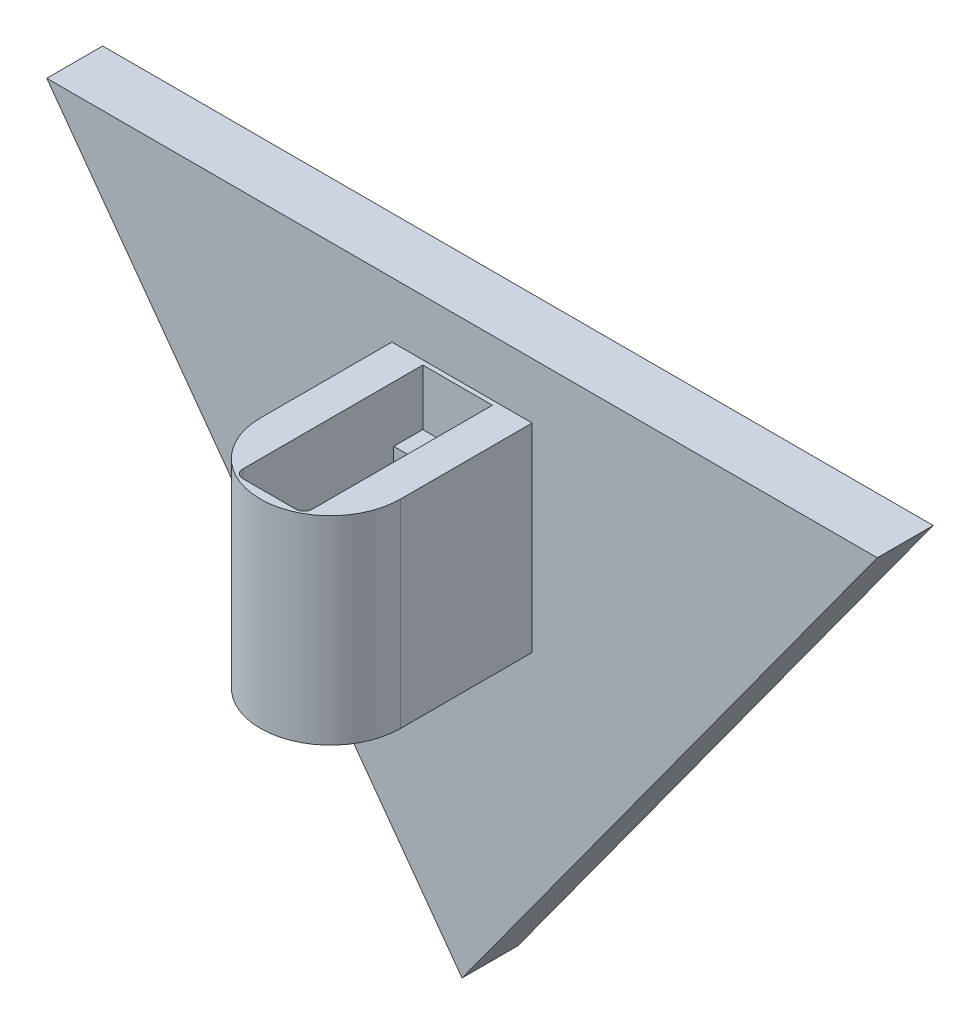
SolidWorks part; units mm, degrees
ref_plane "Front Plane" through (0, 0, 0) normal (0, 0, 1) x (1, 0, 0)
ref_plane "Top Plane" through (0, 0, 0) normal (0, 1, 0) x (1, 0, 0)
ref_plane "Right Plane" through (0, 0, 0) normal (1, 0, 0) x (0, 0, -1)
sketch "Sketch4" plane through (0, 0, 0) normal (0, 0, 1) x (1, 0, 0)
  line L0 (55, 0) -> (-55, 0) construction
  line L1 (-6.23, -9.975) -> (6.23, -9.975)
  line L2 (-6.23, -9.975) -> (-6.23, 7.275)
  line L3 (-6.23, 7.275) -> (6.23, 7.275)
  line L4 (6.23, -9.975) -> (6.23, 7.275)
  point P4 (0, 7.275)
  dimension "D1" = 12.46
  dimension "D2" = 17.25
  dimension "D3" = 9.975
extrude "Boss-Extrude3" add sketch "Sketch4" along normal blind 6
sketch "Sketch8" plane through (0, -9.975, 0) normal (0, -1, 0) x (-1, 0, 0)
  circle A0 centre (0, -23.55) radius 12.5468
  circle A1 centre (0, -23.55) radius 11.15
  dimension "D1" = 22.3
  dimension "D2" = 23.55
extrude "Boss-Extrude6" add sketch "Sketch8" along normal blind 8.3 and the other way up to surface (17.25 mm away) other way up to face at (0, 7.275, 3)
sketch "Sketch5" plane through (0, 7.275, 0) normal (0, 1, 0) x (1, 0, 0)
  line L8 (12.5468, -23.55) -> (12.5468, 0)
  line L9 (12.5468, 0) -> (6.23, 0)
  line L10 (-12.5468, -23.55) -> (-12.5468, 0)
  line L11 (-12.5468, 0) -> (-6.23, 0)
  line L12 (-6.23, 0) -> (-6.23, -29.7)
  line L14 (6.23, -29.7) -> (6.23, 0)
  line L15 (-6.23, -29.7) -> (6.23, -29.7)
  line L16 (6.23, -6) -> (-6.23, -6) construction
  circle A0 centre (0, -23.55) radius 12.5468 construction
  arc A1 (-12.5468, -23.55) -> (12.5468, -23.55) centre (0, -23.55) ccw
  dimension "D1" = 23.7
  dimension "D2" = 23.55
extrude "Boss-Extrude4" add sketch "Sketch5" against normal up to surface (17.25 mm away) up to face at (0, -9.975, 3)
sketch "Sketch6" plane through (0, 7.275, 0) normal (0, 1, 0) x (1, 0, 0)
  line L0 (6.23, -6) -> (-6.23, -6) construction
  line L3 (6.23, -29.7) -> (-6.23, -29.7) construction
  circle A0 centre (0, -3.6) radius 0.75
  circle A1 centre (0, -32.1) radius 0.75
  dimension "D1" = 1.5
  dimension "D3" = 1.5
  dimension "D2" = 2.4
  dimension "D4" = 2.4
extrude "Cut-Extrude1" cut sketch "Sketch6" against normal blind 5
chamfer "Chamfer1" distance 0.5 angle 60 2 edges at (0, 7.275, 4.35) (0, 7.275, 32.85) first distance on face at (0, 7.275, 4.35)
sketch "Sketch10" plane through (0, 7.275, 0) normal (0, 1, 0) x (1, 0, 0)
  line L1 (-6.23, -6) -> (6.23, -6)
  line L2 (-6.23, -6) -> (-6.23, -29.7)
  line L3 (-6.23, -29.7) -> (6.23, -29.7)
  line L4 (6.23, -6) -> (6.23, -29.7)
extrude "Cut-Extrude3" cut sketch "Sketch10" against normal up to surface (17.25 mm away) up to face at (0, -9.975, 10.3399)
ref_plane "Plane1" through (0, 0, 36.0968) normal (0, 0, 1) x (1, 0, 0)
sketch "Sketch13" plane through (0, -18.275, 0) normal (0, -1, 0) x (1, 0, 0)
  line L0 (-12.5468, 23.55) -> (-12.5468, 0)
  line L1 (-12.5468, 0) -> (12.5468, 0)
  line L2 (12.5468, 0) -> (12.5468, 23.55)
  arc A0 (-12.5468, 23.55) -> (12.5468, 23.55) centre (0, 23.55) ccw
  point P3 (0, 0)
extrude "Boss-Extrude7" add sketch "Sketch13" against normal up to surface (8.3 mm away) up to face at (0, -9.975, 10.3399)
sketch "Sketch15" plane through (0, 7.275, 0) normal (0, 1, 0) x (1, 0, 0)
  line L0 (-12.5468, 0) -> (12.5468, 0)
  line L1 (12.5468, 0) -> (12.5468, -23.55)
  line L2 (-12.5468, 0) -> (-12.5468, -23.55)
  line L3 (6.23, -6) -> (6.23, -29.7) construction
  line L4 (-6.23, -0.8) -> (6.23, -0.8)
  line L5 (-6.23, -0.8) -> (-6.23, -33)
  line L6 (-4.73, -34.5) -> (4.73, -34.5)
  line L7 (6.23, -0.8) -> (6.23, -33)
  arc A0 (-12.5468, -23.55) -> (12.5468, -23.55) centre (0, -23.55) ccw
  circle A1 centre (0, -3.6) radius 0.75 construction
  arc A2 (4.73, -34.5) -> (6.23, -33) centre (4.73, -33) ccw
  arc A3 (-6.23, -33) -> (-4.73, -34.5) centre (-4.73, -33) ccw
  point P15 (0, -0.8)
  dimension "D1" = 0.8
  dimension "D3" = 1.5
  dimension "D2" = 2.8
  dimension "D4" = 0
  dimension "D5" = 34.5
extrude "Boss-Extrude9" add sketch "Sketch15" along normal blind 10
sketch "Sketch16" plane through (0, -18.275, 0) normal (0, -1, 0) x (1, 0, 0)
  circle A0 centre (0, 23.55) radius 11.15
  circle A1 centre (0, 23.55) radius 7.2
  circle A2 centre (0, 23.55) radius 11.15 construction
  dimension "D1" = 14.4
extrude "Boss-Extrude10" add sketch "Sketch16" against normal up to surface (8.3 mm away) up to face at (0, -9.975, 27.1007)
sketch "Sketch17" plane through (0, -18.275, 0) normal (0, -1, 0) x (1, 0, 0)
  circle A0 centre (0, 23.55) radius 10.2
  circle A1 centre (0, 23.55) radius 7.2
  circle A2 centre (0, 23.55) radius 7.2 construction
  dimension "D1" = 20.4
extrude "Cut-Extrude5" cut sketch "Sketch17" against normal blind 1.3
sketch "Sketch11" plane through (0, 0, 29.7) normal (0, 0, 1) x (1, 0, 0)
  line L6 (-5, -9.975) -> (5, -9.975)
  line L7 (-5, -9.975) -> (-5, -11.975)
  line L8 (-5, -11.975) -> (5, -11.975)
  line L9 (5, -9.975) -> (5, -11.975)
  dimension "D2" = 2
  dimension "D4" = 10
extrude "Cut-Extrude4" cut sketch "Sketch11" along direction (0, 0, 1) on the side against the normal up to surface (23.7 mm away) up to face at (0, -1.35, 6)
sketch "Sketch19" plane through (0, -18.275, 0) normal (0, -1, 0) x (1, 0, 0)
  line L0 (6.23, 6) -> (6.23, 29.7) construction
  line L1 (-6.23, 6) -> (6.23, 6)
  line L2 (-6.23, 6) -> (-6.23, 11)
  line L3 (-6.23, 11) -> (6.23, 11)
  line L4 (6.23, 6) -> (6.23, 11)
  dimension "D1" = 5
extrude "Cut-Extrude7" cut sketch "Sketch19" against normal up to next
sketch "Sketch1" plane through (0, 0, 0) normal (0, 0, 1) x (1, 0, 0)
  line L0 (0, -75) -> (74.3071, 27.275)
  line L1 (74.3071, 27.275) -> (-74.3071, 27.275)
  line L2 (-74.3071, 27.275) -> (0, -75)
  line L3 (6.23, 17.275) -> (-6.23, 17.275) construction
  line L4 (25.3532, 0) -> (-25.3532, 0) construction
  point P10 (0, 27.275)
  dimension "D2" = 10
  dimension "D1" = 72
  dimension "D3" = 75
extrude "Offset R" add sketch "Sketch1" against normal blind 10 contours L2 L0 L1
